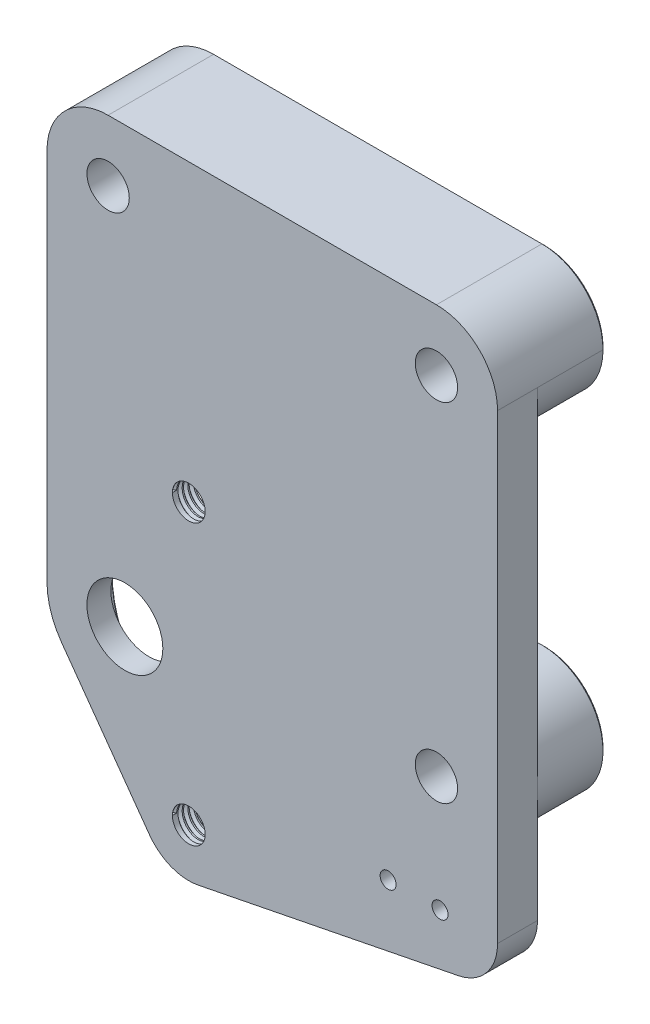
SolidWorks part; units mm, degrees
ref_plane "Front Plane" through (0, 0, 0) normal (0, 0, 1) x (1, 0, 0)
ref_plane "Top Plane" through (0, 0, 0) normal (0, 1, 0) x (1, 0, 0)
ref_plane "Right Plane" through (0, 0, 0) normal (1, 0, 0) x (0, 0, -1)
sketch "Sketch1" plane through (0, 0, 0) normal (0, 0, 1) x (1, 0, 0)
  line L0 (-41.1, 21.74) -> (0, 21.74) construction
  line L1 (0, 21.74) -> (0, -21.74) construction
  line L2 (-31, -25) -> (-39, -25) construction
  line L3 (-41, -23.5) -> (-37, -23.5) construction
  line L4 (-31, -25) -> (-12, -25) construction
  line L5 (-31, -25) -> (-31, -17.5) construction
  line L6 (-31, -17.5) -> (-12, -17.5) construction
  line L7 (-12, -25) -> (-12, -17.5) construction
  line L8 (-31, -25) -> (-12, -25) construction
  line L9 (-31, -25) -> (-31, -32.5) construction
  line L10 (-31, -32.5) -> (-12, -32.5) construction
  line L11 (-12, -25) -> (-12, -32.5) construction
  line L12 (-41, -26.5) -> (-37, -26.5) construction
  line L13 (-31, -42.5) -> (-31, -7.5) construction
  line L14 (-27.5, -7.5) -> (-27.5, -11.4446) construction
  line L15 (-34.5, -7.5) -> (-34.5, -11.4446) construction
  line L16 (-27.5, -42.5) -> (-27.5, -38.5554) construction
  line L17 (-34.5, -42.5) -> (-34.5, -38.5554) construction
  line L23 (-16.5, 74.5503) -> (-16.5, -75.4497) construction
  line L36 (-50, -10) -> (50, -10) construction
  line L37 (-50, -10) -> (-50, 10) construction
  line L38 (-50, 10) -> (50, 10) construction
  line L39 (50, -10) -> (50, 10) construction
  line L40 (-50, -10) -> (50, 10) construction
  line L41 (-50, 10) -> (50, -10) construction
  line L42 (-24, 74.5503) -> (-9, 74.5503) construction
  line L43 (-24, 74.5503) -> (-24, -75.4497) construction
  line L44 (-24, -75.4497) -> (-9, -75.4497) construction
  line L45 (-9, 74.5503) -> (-9, -75.4497) construction
  line L46 (-41.1, 29.39) -> (0, 29.39)
  line L47 (-35.916, -46.0264) -> (-46.9224, -30.6831)
  line L48 (-48.75, -25) -> (-48.75, 21.74)
  line L49 (-27.8523, -47.6667) -> (3.9802, -28.273)
  line L50 (7.65, 21.74) -> (7.65, -21.74)
  line L51 (-48.75, 14.09) -> (7.65, 14.09) construction
  line L52 (-7.05, -34.9931) -> (-7.05, -40.9931)
  line L53 (-7.05, -40.9931) -> (7.65, -40.9931)
  line L54 (7.65, -40.9931) -> (7.65, -12.4946)
  line L55 (0.45, -35.9931) -> (-6.05, -35.9931) construction
  line L56 (-29.8216, -48.4341) -> (7.65, -40.9931)
  circle A0 centre (-41.1, 21.74) radius 12 construction
  circle A1 centre (-41.1, 21.74) radius 2.65
  circle A2 centre (0, 21.74) radius 12 construction
  circle A3 centre (0, 21.74) radius 2.65
  circle A4 centre (0, -21.74) radius 12 construction
  circle A5 centre (0, -21.74) radius 2.65
  circle A6 centre (-31, -25) radius 14 construction
  circle A7 centre (-39, -25) radius 4.75
  circle A8 centre (-39, -25) radius 2.5 construction
  circle A9 centre (-31, -7.5) radius 2.05
  circle A10 centre (-31, -7.5) radius 3.5 construction
  circle A11 centre (-31, -42.5) radius 3.5 construction
  circle A12 centre (-31, -42.5) radius 2.05
  circle A13 centre (-39, -25) radius 15 construction
  circle A16 centre (-41.1, 21.74) radius 7.65
  circle A17 centre (0, 21.74) radius 7.65
  circle A18 centre (0, -21.74) radius 7.65
  circle A20 centre (-31, -42.5) radius 6.05
  circle A21 centre (-39, -25) radius 9.75
  circle A22 centre (-6.05, -35.9931) radius 1
  circle A23 centre (0.45, -35.9931) radius 1
  point P11 (0, 0)
  point P33 (0, 0)
  point P35 (0, 0)
  point P43 (0, 0)
  point P44 (0, 96.9547)
  dimension "D1" = 24
  dimension "D2" = 5.3
  dimension "D3" = 24
  dimension "D4" = 5.3
  dimension "D5" = 24
  dimension "D6" = 5.3
  dimension "D7" = 43.48
  dimension "D9" = 28
  dimension "D13" = 9.5
  dimension "D14" = 5
  dimension "D16" = 4.1
  dimension "D17" = 7
  dimension "D32" = 30
  dimension "D45" = 2
  dimension "D8" = 41.1
  dimension "D10" = 8
  dimension "D11" = 7.5
  dimension "D12" = 19
  dimension "D15" = 1.5
  dimension "D18" = 17.5
  dimension "D28" = 20
  dimension "D29" = 100
  dimension "D30" = 15
  dimension "D31" = 15
  dimension "D36" = 150
  dimension "D42" = 39
  dimension "D43" = 14.7
  dimension "D44" = 6
  dimension "D46" = 1
  dimension "D47" = 5
  dimension "D38" = 5
  dimension "D39" = 5
  dimension "D40" = 4
  dimension "D41" = 5
extrude "Boss-Extrude1" add sketch "Sketch1" along normal blind 5 contours A21 L47 A20 L49 A18 L50 A17 L46 A16 L48 A9 | A16 A1 | A17 A3 | A18 A5 | A20 A12 | A21 A7 | A18 L49 L52 L53 L54 | L49 A20 L56 L53 L52 region at (-20.5785, -3.8476, 0) region at (-35.8436, 26.9964, 0) region at (5.2564, 26.9964, 0) region at (-39, -15.5258, 0) region at (6.4811, -25.3806, 0) region at (1.6273, -35.2213, 0) region at (-32.7998, -36.9034, 0) region at (-12.0976, -42.3056, 0)
sketch "Sketch2" plane through (0, 0, 0) normal (0, 0, -1) x (-1, 0, 0)
  line L0 (48.75, 14.09) -> (-7.65, 14.09) construction
  line L1 (48.75, 14.09) -> (-7.65, 14.09)
  circle A0 centre (0, -21.74) radius 7.65 construction
  circle A1 centre (31, -42.5) radius 2.05
  circle A2 centre (31, -42.5) radius 2.05
  circle A3 centre (39, -25) radius 4.75
  circle A4 centre (39, -25) radius 4.75
  circle A5 centre (0, -21.74) radius 2.65
  circle A6 centre (0, -21.74) radius 2.65
  circle A7 centre (0, 21.74) radius 2.65
  circle A8 centre (0, 21.74) radius 2.65
  circle A9 centre (41.1, 21.74) radius 2.65
  circle A10 centre (41.1, 21.74) radius 2.65
  circle A11 centre (31, -7.5) radius 2.05
  circle A12 centre (31, -7.5) radius 2.05
  circle A13 centre (0, -21.74) radius 7.65
  line M7 (48.75, -25) -> (48.75, 21.74)
  arc M8 (48.75, 21.74) -> (41.1, 29.39) centre (41.1, 21.74) ccw
  line M9 (41.1, 29.39) -> (0, 29.39)
  arc M10 (0, 29.39) -> (-7.65, 21.74) centre (0, 21.74) ccw
  line M11 (-7.65, 21.74) -> (-7.65, -40.9931)
  circle M18 centre (41.1, 21.74) radius 2.65
  circle M19 centre (0, 21.74) radius 2.65
  circle M20 centre (0, -21.74) radius 2.65
  dimension "D1" = 0
  dimension "D2" = 0
  dimension "D3" = 0
  dimension "D4" = 0
  dimension "D5" = 0
  dimension "D6" = 0
extrude "Boss-Extrude2" add sketch "Sketch2" along normal blind 8.5 contours L1 M7 M8 M9 M10 M11 M19 M18 | A13 M20 region at (0, -14.3064, 0) region at (-20.55, 21.552, 0)
sketch "Sketch7" plane through (0, 0, 0) normal (0, 0, -1) x (-1, 0, 0)
  line L0 (27.5, -42.5) -> (27.5, -38.5554) construction
  line L1 (34.5, -42.5) -> (34.5, -38.5554) construction
  line L2 (27.5, -7.5) -> (27.5, -11.4446) construction
  line L3 (34.5, -7.5) -> (34.5, -11.4446) construction
  line L4 (27.5, -42.5) -> (27.5, -38.5554)
  line L5 (34.5, -42.5) -> (34.5, -38.5554)
  line L6 (27.5, -7.5) -> (27.5, -11.4446)
  line L7 (34.5, -7.5) -> (34.5, -11.4446)
  line L12 (12, -25) -> (12, -32.5) construction
  line L13 (31, -32.5) -> (12, -32.5) construction
  line L14 (12, -25) -> (12, -17.5) construction
  line L15 (31, -17.5) -> (12, -17.5) construction
  line L16 (12, -25) -> (12, -32.5)
  line L17 (19.1784, -32.5) -> (12, -32.5)
  line L18 (12, -25) -> (12, -17.5)
  line L19 (19.1784, -17.5) -> (12, -17.5)
  line L20 (19.0146, -17.2) -> (11.7, -17.2)
  line L21 (11.7, -25) -> (11.7, -17.2)
  line L22 (11.7, -25) -> (11.7, -32.8)
  line L23 (19.0146, -32.8) -> (11.7, -32.8)
  line L24 (27.2, -42.5) -> (27.2, -38.7859)
  line L25 (34.8, -42.5) -> (34.8, -38.7859)
  line L26 (34.8, -7.5) -> (34.8, -11.2141)
  line L27 (27.2, -7.5) -> (27.2, -11.2141)
  circle A0 centre (31, -42.5) radius 3.5 construction
  circle A1 centre (31, -7.5) radius 3.5 construction
  circle A2 centre (31, -25) radius 14 construction
  arc A3 (27.5, -42.5) -> (34.5, -42.5) centre (31, -42.5) ccw
  arc A4 (34.5, -7.5) -> (27.5, -7.5) centre (31, -7.5) ccw
  arc A5 (34.5, -38.5554) -> (34.5, -11.4446) centre (31, -25) ccw
  arc A6 (27.5, -11.4446) -> (19.1784, -17.5) centre (31, -25) ccw
  arc A11 (19.1784, -32.5) -> (27.5, -38.5554) centre (31, -25) ccw
  arc A12 (27.2, -11.2141) -> (19.0146, -17.2) centre (31, -25) ccw
  arc A13 (19.0146, -32.8) -> (27.2, -38.7859) centre (31, -25) ccw
  arc A14 (27.2, -42.5) -> (34.8, -42.5) centre (31, -42.5) ccw
  arc A15 (34.8, -38.7859) -> (34.8, -11.2141) centre (31, -25) ccw
  arc A16 (34.8, -7.5) -> (27.2, -7.5) centre (31, -7.5) ccw
  circle M9 centre (31, -7.5) radius 2.05
  circle M10 centre (31, -42.5) radius 2.05
  circle M11 centre (39, -25) radius 4.75
  dimension "D1" = 0.3
extrude "Cut-Extrude1" cut sketch "Sketch7" against normal blind 2 contours L6 A6 L4 A3 L5 A5 L7 A4 M10 M11 M9 | A12 L19 A6 L6 A4 L7 A5 L5 A3 L4 region at (-28.1953, -25, 0) region at (-22.5909, -13.5009, 0)
fillet "Fillet1" radius 2 8 edges at (-19.0146, -32.8, 1) (-34.8, -38.7859, 1) (-27.2, -38.7859, 1) (-34.8, -11.2141, 1) (-27.2, -11.2141, 1) (-19.0146, -17.2, 1) (-11.7, -32.8, 1) (-11.7, -17.2, 1)
thread "Thread1" pitch 0.7 method cut profile "Thread Profile1" start angle 0, offset 0, length 10, pitch 0.7, diameter 4.1
ref_plane "Plane1" through (-33.05, -7.5, 5) normal (0, -1, 0) x (-1, 0, 0)
sketch "Thread Profile1" plane through (-33.05, -7.5, 5) normal (0, -1, 0) x (-1, 0, 0)
  line L0 (0, 0) -> (0, 0.7) construction
  line L1 (0, 0) -> (0.3789, 0.2187)
  line L2 (0.3789, 0.2187) -> (0.3789, 0.3062)
  line L3 (0.3789, 0.3062) -> (0, 0.525)
  line L4 (0.3789, 0.2625) -> (0, 0.2625) construction
  line L11 (0, 0) -> (0, 0.525)
  point P2 (0, 0)
  dimension "Pitch" = 0.7
  dimension "Profile_Angle" = 60
  dimension "Profile_Land" = 0.0875
  dimension "Profile_Height" = 0.3789
thread "Thread2" pitch 0.7 method cut profile "Thread Profile2" start angle 0, offset 0, length 10, pitch 0.7, diameter 4.1
ref_plane "Plane2" through (-33.05, -42.5, 5) normal (0, -1, 0) x (-1, 0, 0)
sketch "Thread Profile2" plane through (-33.05, -42.5, 5) normal (0, -1, 0) x (-1, 0, 0)
  line L0 (0, 0) -> (0, 0.7) construction
  line L1 (0, 0) -> (0.3789, 0.2187)
  line L2 (0.3789, 0.2187) -> (0.3789, 0.3062)
  line L3 (0.3789, 0.3062) -> (0, 0.525)
  line L4 (0.3789, 0.2625) -> (0, 0.2625) construction
  line L11 (0, 0) -> (0, 0.525)
  point P2 (0, 0)
  dimension "Pitch" = 0.7
  dimension "Profile_Angle" = 60
  dimension "Profile_Land" = 0.0875
  dimension "Profile_Height" = 0.3789
fillet "Fillet2" radius 7.65 2 edges at (7.65, 14.09, -4.25) (-48.75, 14.09, -4.25)
sketch "Sketch10" plane through (0, 0, -8.5) normal (0, 0, -1) x (-1, 0, 0)
  line L0 (0, 14.09) -> (41.1, 14.09) construction
  line L1 (41.1, 29.39) -> (0, 29.39) construction
  line L2 (0, 14.09) -> (41.1, 14.09)
  line L3 (41.1, 29.39) -> (0, 29.39)
  circle A1 centre (0, -21.74) radius 2.65
  circle A2 centre (0, -21.74) radius 2.65
  circle A3 centre (41.1, 21.74) radius 2.65
  circle A4 centre (41.1, 21.74) radius 2.65
  circle A5 centre (0, 21.74) radius 2.65
  circle A6 centre (0, 21.74) radius 2.65
  arc A7 (0, 29.39) -> (-7.65, 21.74) centre (0, 21.74) ccw construction
  arc A8 (-7.65, 21.74) -> (0, 14.09) centre (0, 21.74) ccw construction
  arc A9 (41.1, 14.09) -> (48.75, 21.74) centre (41.1, 21.74) ccw construction
  arc A10 (48.75, 21.74) -> (41.1, 29.39) centre (41.1, 21.74) ccw construction
  arc A12 (0, 29.39) -> (-7.65, 21.74) centre (0, 21.74) ccw
  arc A13 (-7.65, 21.74) -> (0, 14.09) centre (0, 21.74) ccw
  arc A14 (41.1, 14.09) -> (48.75, 21.74) centre (41.1, 21.74) ccw
  arc A15 (48.75, 21.74) -> (41.1, 29.39) centre (41.1, 21.74) ccw
  circle A16 centre (0, 21.74) radius 4
  circle A17 centre (41.1, 21.74) radius 4
  circle A18 centre (0, -21.74) radius 4
  circle M10 centre (0, 21.74) radius 2.65
  circle M11 centre (41.1, 21.74) radius 2.65
  dimension "D4" = 8
  dimension "D5" = 8
  dimension "D1" = 0
  dimension "D2" = 0
  dimension "D3" = 0
extrude "Boss-Extrude5" add sketch "Sketch10" along normal blind 1 contours A18 A2 | M10 | A17 M11 | A16 region at (0, 21.74, -8.5) region at (-37.2131, 21.74, -8.5) region at (3.8869, -21.74, -8.5)
chamfer "Chamfer2" distance 0.3 angle 45 30 edges at (-20.55, 14.09, -8.5) (-46.5094, 16.3306, -8.5) (5.4094, 16.3306, -8.5) (-46.5094, 27.1494, -8.5) (5.4094, 27.1494, -8.5) (-20.55, 29.39, -8.5) (-4, -21.74, -8.5) (-4, 21.74, -8.5) (-45.1, 21.74, -8.5) (-22.4054, -13.571, 0) (-7.65, -21.74, -8.5) (-11.7, -25, 0) (-15.8375, -17.2, 0) (-18.8681, -16.9895, 0) (-26.8467, -10.9019, 0) (-27.2, -8.6334, 0) (-31, -3.7, 0) (-34.8, -8.6334, 0) (-35.1533, -10.9019, 0) (-45.3, -25, 0) (-35.1533, -39.0981, 0) (-34.8, -41.3666, 0) (-31, -46.3, 0) (-15.8375, -32.8, 0) (-27.2, -41.3666, 0) (-18.8681, -33.0105, 0) (-26.8467, -39.0981, 0) (-22.4054, -36.429, 0) (-12.2858, -17.7858, 0) (-12.2858, -32.2142, 0)
fillet "Fillet3" radius 6.05 1 edges at (7.65, -40.9931, 2.5)
